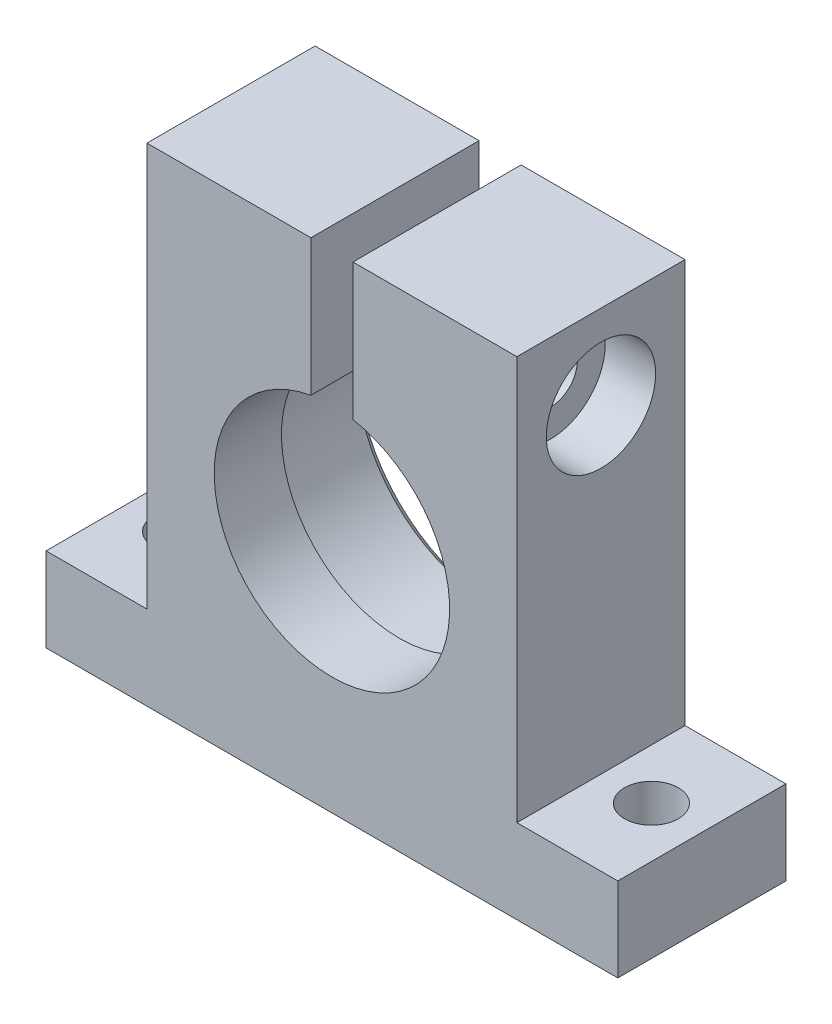
SolidWorks part; units mm, degrees
material "AISI 1045 Steel, cold drawn"
ref_plane "Front Plane" through (0, 0, 0) normal (0, 0, 1) x (1, 0, 0)
ref_plane "Top Plane" through (0, 0, 0) normal (0, 1, 0) x (1, 0, 0)
ref_plane "Right Plane" through (0, 0, 0) normal (1, 0, 0) x (0, 0, -1)
sketch "Sketch1" plane through (0, 0, 0) normal (0, 0, 1) x (1, 0, 0)
  line L1 (11, -14) -> (-11, -14)
  line L2 (11, -14) -> (11, 15)
  line L3 (11, 15) -> (-11, 15)
  line L4 (-11, -14) -> (-11, 15)
  line L5 (11, -14) -> (-11, 15) construction
  line L6 (11, 15) -> (-11, -14) construction
  circle A0 centre (0, 0) radius 8 construction
  point P3 (0, 0.5)
  dimension "D1" = 16
  dimension "D2" = 29
  dimension "D3" = 15
  dimension "D4" = 22
extrude "Boss-Extrude1" add sketch "Sketch1" along normal mid plane 10
sketch "Sketch3" plane through (0, -14, 0) normal (0, -1, 0) x (1, 0, 0)
  line L0 (-11, 5) -> (11, 5) construction
  line L1 (17, -5) -> (-17, -5)
  line L2 (17, -5) -> (17, 5)
  line L3 (17, 5) -> (-17, 5)
  line L4 (-17, -5) -> (-17, 5)
  line L5 (17, -5) -> (-17, 5) construction
  line L6 (17, 5) -> (-17, -5) construction
  point P0 (0, 0)
  dimension "D1" = 34
extrude "Boss-Extrude2" add sketch "Sketch3" against normal blind 5
hole_wizard "Ø16.0 (16) Diameter Hole1" positions "Sketch4" profile "Sketch5" hole size "Ø16.0" standard "ANSI Metric"
sketch "Sketch4" plane through (0, 0, -5) normal (0, 0, -1) x (-1, 0, 0)
  point P0 (0, 0)
sketch "Sketch5" plane through (0, 0, -5) normal (1, 0, 0) x (0, 1, 0)
  line L0 (0, 0) -> (0, 6)
  line L1 (0, 6) -> (8, 6)
  line L2 (8, 6) -> (8, 0)
  line L5 (8, 0) -> (0, 0)
  line L10 (0, 6) -> (-8, 6) construction
  line L11 (0, -6.35) -> (0, 107.95) construction
  dimension "Hole Dia." = 16
  dimension "Hole Depth" = 6
  dimension "Drill Angle" = 180
hole_wizard "Ø14.0 (14) Diameter Hole1" positions "Sketch13" profile "Sketch14" hole size "Ø14.0" standard "ANSI Metric" end condition through all
sketch "Sketch13" plane through (0, 0, 1) normal (0, 0, -1) x (-1, 0, 0)
  point P0 (0, 0)
sketch "Sketch14" plane through (0, 0, 1) normal (1, 0, 0) x (0, 1, 0)
  line L0 (0, 0) -> (0, 4)
  line L1 (0, 4) -> (7, 4)
  line L2 (7, 4) -> (7, 0)
  line L5 (7, 0) -> (0, 0)
  line L11 (0, -6.35) -> (0, 107.95) construction
  dimension "Thru Hole Dia." = 14
  dimension "Thru Hole Depth" = 4
hole_wizard "M3 Clearance Hole1" positions "Sketch6" profile "Sketch7" hole size "M3" standard "ANSI Metric" end condition through all
sketch "Sketch6" plane through (0, -9, 0) normal (0, 1, 0) x (1, 0, 0)
  line L0 (-17, -5) -> (-11, 5) construction
  line L2 (17, -5) -> (11, 5) construction
  point P0 (-14, 0)
  point P2 (14, 0)
sketch "Sketch7" plane through (-14, -9, 0) normal (1, 0, 0) x (0, 0, 1)
  line L0 (0, 0) -> (0, 5)
  line L1 (0, 5) -> (1.6, 5)
  line L2 (1.6, 5) -> (1.6, 0)
  line L5 (1.6, 0) -> (0, 0)
  line L11 (0, -6.35) -> (0, 107.95) construction
  dimension "Thru Hole Dia." = 3.2
  dimension "Thru Hole Depth" = 5
sketch "Sketch12" plane through (0, 0, 5) normal (0, 0, 1) x (1, 0, 0)
  line L0 (11, 15) -> (-11, 15) construction
  line L1 (1.25, 6.8875) -> (-1.25, 6.8875)
  line L2 (1.25, 6.8875) -> (1.25, 15)
  line L3 (1.25, 15) -> (-1.25, 15)
  line L4 (-1.25, 6.8875) -> (-1.25, 15)
  line L5 (1.25, 6.8875) -> (-1.25, 15) construction
  line L6 (1.25, 15) -> (-1.25, 6.8875) construction
  circle A1 centre (0, 0) radius 7 construction
  point P0 (0, 10.9437)
  dimension "D1" = 2.5
extrude "Cut-Extrude1" cut sketch "Sketch12" against normal through all
hole_wizard "M3x0.5 Tapped Hole1" positions "Sketch8" profile "Sketch9" tap size "M3x0.5" standard "ANSI Metric" end condition up to next
sketch "Sketch8" plane through (-11, 0, 0) normal (-1, 0, 0) x (0, 0, 1)
  line L0 (5, 15) -> (-5, 15) construction
  point P0 (0, 10)
  dimension "D1" = 5
cosmetic thread "Hole Thread2" parameters "D2"=3
sketch "Sketch9" plane through (-11, 10, 0) normal (0, 1, 0) x (0, 0, 1)
  line L0 (0, 0) -> (0, 9.75)
  line L1 (0, 9.75) -> (1.25, 9.75)
  line L2 (1.25, 9.75) -> (1.25, 0)
  line L5 (1.25, 0) -> (0, 0)
  line L11 (0, -6.35) -> (0, 107.95) construction
  dimension "Thru Tap Drill Dia." = 2.5
  dimension "Thru Tap Drill Depth" = 9.75
hole_wizard "CBORE for M3 SHCS1" positions "Sketch10" profile "Sketch11" counterbore size "M3" standard "ANSI Metric" end condition up to next
sketch "Sketch10" plane through (11, 0, 0) normal (1, 0, 0) x (0, 0, -1)
  point P0 (0, 10)
sketch "Sketch11" plane through (11, 10, 0) normal (0, 1, 0) x (0, 0, -1)
  line L0 (0, 0) -> (0, 9.75)
  line L1 (0, 9.75) -> (1.6, 9.75)
  line L3 (1.6, 9.75) -> (1.6, 3)
  line L4 (1.6, 3) -> (3.25, 3)
  line L5 (3.25, 3) -> (3.25, 0)
  line L7 (3.25, 0) -> (0, 0)
  line L11 (0, -6.35) -> (0, 107.95) construction
  dimension "Thru Hole Dia." = 3.2
  dimension "Thru Hole Depth" = 9.75
  dimension "C'Bore Dia." = 6.5
  dimension "C'Bore Depth" = 3
chamfer "Chamfer1" distance 0.5 angle 45 1 edges at (0, -8, -5)
